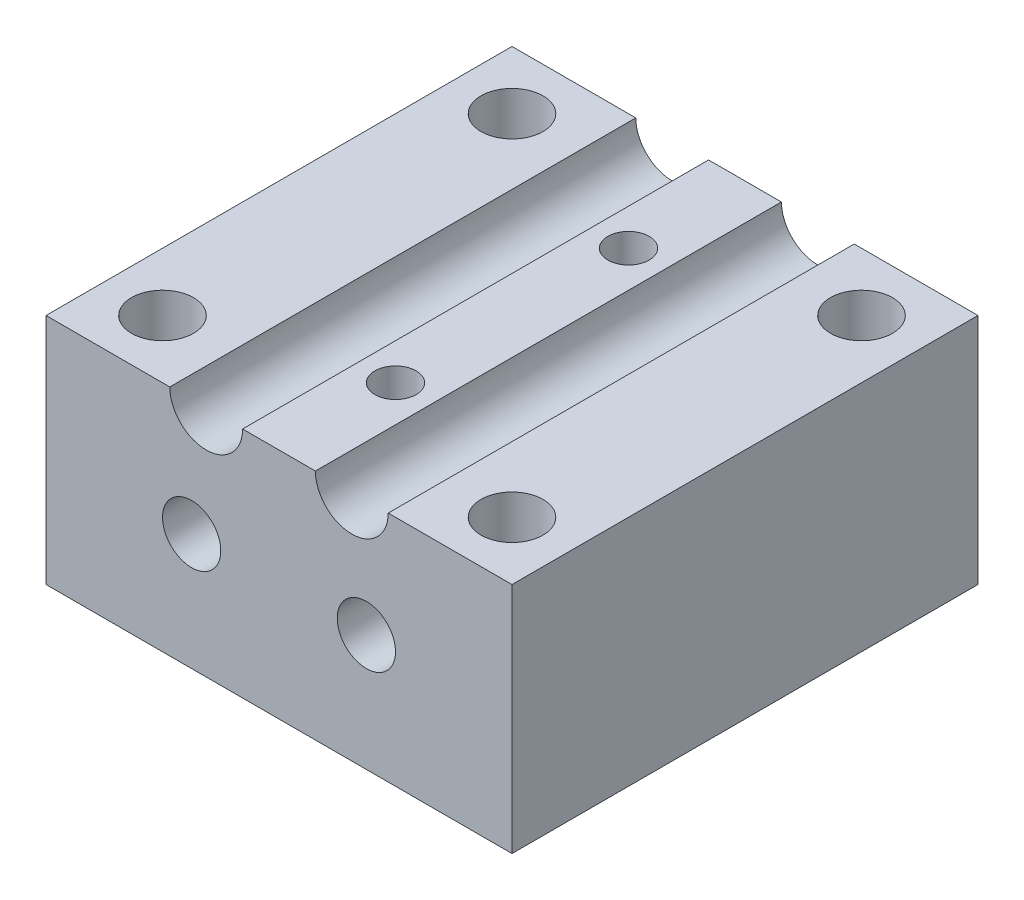
SolidWorks part; units mm, degrees
ref_plane "Front Plane" through (0, 0, 0) normal (0, 0, 1) x (1, 0, 0)
ref_plane "Top Plane" through (0, 0, 0) normal (0, 1, 0) x (1, 0, 0)
ref_plane "Right Plane" through (0, 0, 0) normal (1, 0, 0) x (0, 0, -1)
sketch "Sketch1" plane through (0, 0, 0) normal (0, 1, 0) x (1, 0, 0)
  line L1 (25.4, 25.4) -> (-25.4, 25.4)
  line L2 (25.4, 25.4) -> (25.4, -25.4)
  line L3 (25.4, -25.4) -> (-25.4, -25.4)
  line L4 (-25.4, 25.4) -> (-25.4, -25.4)
  line L5 (25.4, 25.4) -> (-25.4, -25.4) construction
  line L6 (25.4, -25.4) -> (-25.4, 25.4) construction
  point P0 (0, 0)
  dimension "D1" = 50.8
  dimension "D2" = 50.8
extrude "Boss-Extrude1" add sketch "Sketch1" along normal blind 25.4
sketch "Sketch2" plane through (0, 0, 25.4) normal (0, 0, 1) x (1, 0, 0)
  line L0 (-25.4, 25.4) -> (25.4, 25.4) construction
  line L1 (25.4, 25.4) -> (-25.4, 25.4) construction
  circle A0 centre (-7.9375, 25.4) radius 3.9688
  circle A1 centre (7.9375, 25.4) radius 3.9688
  point P6 (0, 25.4)
  dimension "D1" = 7.9375
  dimension "D2" = 15.875
  dimension "D3" = 7.9375
extrude "Cut-Extrude1" cut sketch "Sketch2" against normal through all
hole_wizard "1/4 Clearance Hole1" positions "Sketch5" profile "Sketch4" hole size "1/4" standard "ANSI Inch" end condition through all
sketch "Sketch5" plane through (0, 25.4, 0) normal (0, 1, 0) x (1, 0, 0)
  point P0 (-19.05, 19.05)
  point P2 (-19.05, -19.05)
  point P4 (19.05, -19.05)
  point P6 (19.05, 19.05)
sketch "Sketch4" plane through (-19.05, 25.4, -19.05) normal (1, 0, 0) x (0, 0, 1)
  line L0 (0, 0) -> (0, 25.4)
  line L1 (0, 25.4) -> (3.3782, 25.4)
  line L2 (3.3782, 25.4) -> (3.3782, 0)
  line L5 (3.3782, 0) -> (0, 0)
  line L11 (0, -6.35) -> (0, 107.95) construction
  dimension "Thru Hole Dia." = 6.7564
  dimension "Thru Hole Depth" = 25.4
sketch "Sketch6" plane through (0, 0, 25.4) normal (0, 0, 1) x (1, 0, 0)
  line L0 (-25.4, 25.4) -> (-11.9063, 25.4) construction
  circle A0 centre (-9.525, 12.7) radius 3.175
  circle A1 centre (9.525, 12.7) radius 3.175
  dimension "D1" = 6.35
  dimension "D2" = 19.05
  dimension "D4" = 9.525
  dimension "D5" = 12.7
extrude "Cut-Extrude2" cut sketch "Sketch6" against normal through all
hole_wizard "#8 Clearance Hole1" positions "Sketch8" profile "Sketch7" hole size "#8" standard "ANSI Inch" end condition through all
sketch "Sketch8" plane through (0, 25.4, 0) normal (0, 1, 0) x (1, 0, 0)
  point P0 (0, 12.7)
  point P2 (0, -12.7)
sketch "Sketch7" plane through (0, 25.4, -12.7) normal (1, 0, 0) x (0, 0, 1)
  line L0 (0, 0) -> (0, 25.4)
  line L1 (0, 25.4) -> (2.2479, 25.4)
  line L2 (2.2479, 25.4) -> (2.2479, 0)
  line L5 (2.2479, 0) -> (0, 0)
  line L11 (0, -6.35) -> (0, 107.95) construction
  dimension "Thru Hole Dia." = 4.4958
  dimension "Thru Hole Depth" = 25.4
